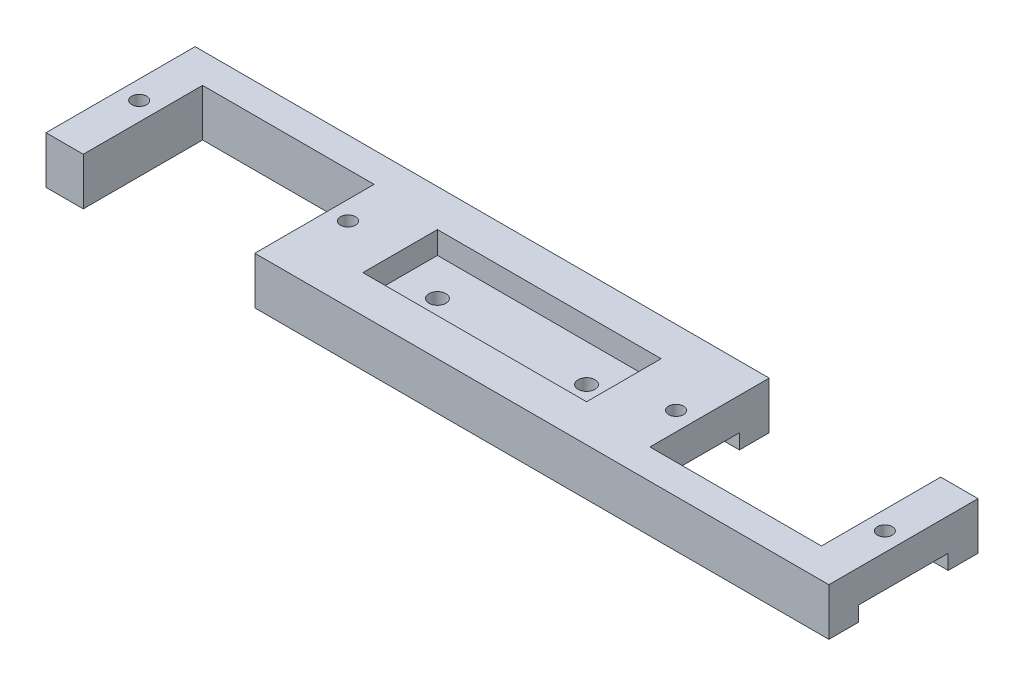
SolidWorks part; units mm, degrees
material "ABS"
ref_plane "Front" through (0, 0, 0) normal (0, 0, 1) x (1, 0, 0)
ref_plane "Top" through (0, 0, 0) normal (0, 1, 0) x (1, 0, 0)
ref_plane "Right" through (0, 0, 0) normal (1, 0, 0) x (0, 0, -1)
sketch "Sketch1" plane through (0, 0, 0) normal (0, 1, 0) x (1, 0, 0)
  line L1 (-52.5, 10) -> (52.5, 10)
  line L2 (-52.5, 10) -> (-52.5, -10)
  line L3 (-52.5, -10) -> (52.5, -10)
  line L4 (52.5, 10) -> (52.5, -10)
  line L5 (-52.5, 10) -> (52.5, -10) construction
  line L6 (-52.5, -10) -> (52.5, 10) construction
  point P0 (0, 0)
  dimension "D1" = 105
  dimension "D2" = 20
extrude "Boss-Extrude1" add sketch "Sketch1" along normal blind 6.35
sketch "Sketch3" plane through (0, 6.35, 0) normal (0, 1, 0) x (1, 0, 0)
  line L0 (-52.5, -10) -> (52.5, -10) construction
  line L1 (-47.5, -10) -> (-24.5, -10)
  line L2 (-47.5, -10) -> (-47.5, 6)
  line L3 (-47.5, 6) -> (-24.5, 6)
  line L4 (-24.5, -10) -> (-24.5, 6)
  line L5 (-52.5, 10) -> (-52.5, -10) construction
  line L6 (52.5, 10) -> (-52.5, 10) construction
  line L7 (52.5, -10) -> (52.5, 10) construction
  line L8 (24.5, 10) -> (47.5, 10)
  line L9 (24.5, 10) -> (24.5, -6)
  line L10 (24.5, -6) -> (47.5, -6)
  line L11 (47.5, 10) -> (47.5, -6)
  dimension "D1" = 23
  dimension "D2" = 5
  dimension "D3" = 4
  dimension "D4" = 5
  dimension "D5" = 4
extrude "Cut-Extrude1" cut sketch "Sketch3" against normal through all
sketch "Sketch4" plane through (0, 0, 0) normal (0, -1, 0) x (1, 0, 0)
  line L0 (24.5, -10) -> (24.5, 6) construction
  line L1 (24.5, 6) -> (19.5, 6)
  line L2 (24.5, 6) -> (24.5, -6)
  line L3 (24.5, -6) -> (19.5, -6)
  line L4 (19.5, 6) -> (19.5, -6)
  line L5 (47.5, 6) -> (47.5, -10) construction
  line L6 (47.5, 6) -> (52.5, 6)
  line L7 (47.5, 6) -> (47.5, -6)
  line L8 (47.5, -6) -> (52.5, -6)
  line L9 (52.5, 6) -> (52.5, -6)
  line L10 (24.5, -10) -> (52.5, 10) construction
  line L11 (24.5, 0) -> (47.5, 0) construction
  point P18 (38.5, 0)
  dimension "D1" = 5
  dimension "D2" = 12
extrude "Cut-Extrude2" cut sketch "Sketch4" against normal blind 2
hole_wizard "M2 Clearance Hole1" positions "Sketch7" profile "Sketch8" hole size "M2" standard "ANSI Metric" end condition through all
sketch "Sketch7" plane through (0, 6.35, 0) normal (0, 1, 0) x (1, 0, 0)
  line L0 (-52.5, 0) -> (52.5, 0) construction
  line L1 (-52.5, 10) -> (-52.5, -10) construction
  line L2 (52.5, -10) -> (52.5, 10) construction
  line L3 (24.5, 10) -> (24.5, -6) construction
  line L4 (47.5, -6) -> (47.5, 10) construction
  line L5 (-47.5, 6) -> (-47.5, -10) construction
  line L6 (-24.5, -10) -> (-24.5, 6) construction
  point P9 (-50, 0)
  point P11 (-22, 0)
  point P13 (22, 0)
  point P15 (50, 0)
  dimension "D1" = 2.5
  dimension "D2" = 2.5
  dimension "D3" = 2.5
  dimension "D4" = 2.5
sketch "Sketch8" plane through (50, 6.35, 0) normal (1, 0, 0) x (0, 0, 1)
  line L0 (0, 0) -> (0, 6.35)
  line L1 (0, 6.35) -> (1, 6.35)
  line L2 (1, 6.35) -> (1, 0)
  line L5 (1, 0) -> (0, 0)
  line L11 (0, -6.35) -> (0, 107.95) construction
  dimension "Thru Hole Dia." = 2
  dimension "Thru Hole Depth" = 6.35
sketch "Sketch9" plane through (0, 6.35, 0) normal (0, 1, 0) x (1, 0, 0)
  line L1 (-15, 5) -> (15, 5)
  line L2 (-15, 5) -> (-15, -5)
  line L3 (-15, -5) -> (15, -5)
  line L4 (15, 5) -> (15, -5)
  line L5 (-15, 5) -> (15, -5) construction
  line L6 (-15, -5) -> (15, 5) construction
  point P0 (0, 0)
  dimension "D1" = 10
  dimension "D2" = 30
extrude "Cut-Extrude3" cut sketch "Sketch9" against normal blind 3
hole_wizard "#2 Clearance Hole1" positions "Sketch12" profile "Sketch14" hole size "#2" standard "ANSI Inch" end condition through all
sketch "Sketch12" plane through (0, 3.35, 0) normal (0, 1, 0) x (1, 0, 0)
  line L0 (-10, 0) -> (10, 0) construction
  point P0 (-10, 0)
  point P2 (10, 0)
  dimension "D1" = 20
sketch "Sketch14" plane through (-10, 3.35, 0) normal (1, 0, 0) x (0, 0, 1)
  line L0 (0, 0) -> (0, 3.35)
  line L1 (0, 3.35) -> (2.032, 3.35)
  line L2 (1.1303, 2.366) -> (1.1303, 0)
  line L5 (1.1303, 0) -> (0, 0)
  line L7 (2.032, 3.35) -> (1.1303, 2.366)
  line L8 (-2.032, 3.35) -> (-1.1303, 2.366) construction
  line L11 (0, -6.35) -> (0, 107.95) construction
  dimension "Thru Hole Dia." = 2.2606
  dimension "Thru Hole Depth" = 3.35
  dimension "Far C'Sink Dia." = 4.064
  dimension "Far C'Sink Angle" = 85
